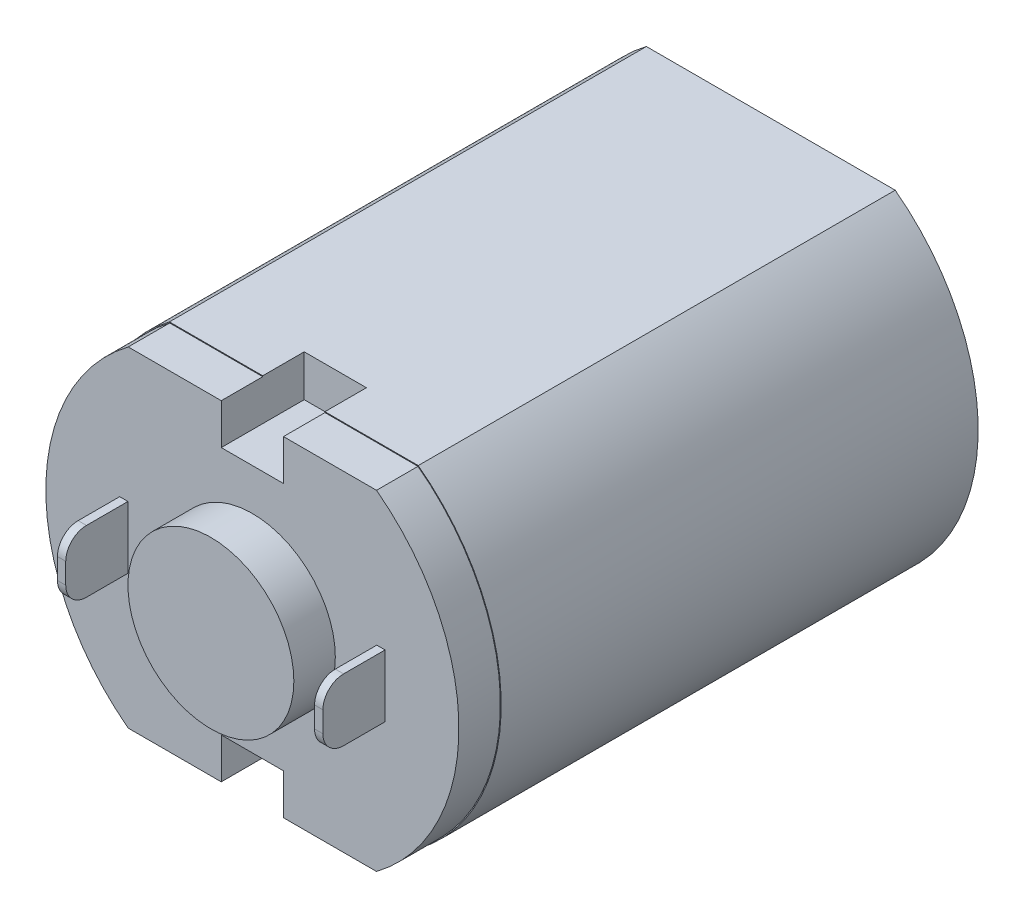
SolidWorks part; units mm, degrees
ref_plane "Front Plane" through (0, 0, 0) normal (0, 0, 1) x (1, 0, 0)
ref_plane "Top Plane" through (0, 0, 0) normal (0, 1, 0) x (1, 0, 0)
ref_plane "Right Plane" through (0, 0, 0) normal (1, 0, 0) x (0, 0, -1)
sketch "Sketch1" plane through (0, 0, 0) normal (0, 0, 1) x (1, 0, 0)
  line L1 (-3, -4) -> (3, -4)
  line L3 (-3, 4) -> (3, 4)
  line L5 (-3, -4) -> (3, 4) construction
  line L6 (-3, 4) -> (3, -4) construction
  arc A0 (-3, 4) -> (-3, -4) centre (0, 0) ccw
  arc A1 (3, -4) -> (3, 4) centre (0, 0) ccw
  dimension "D1" = 10
  dimension "D2" = 8
extrude "Boss-Extrude1" add sketch "Sketch1" along normal blind 12.5
sketch "Sketch2" plane through (0, 0, 0) normal (0, 0, 1) x (1, 0, 0)
  circle A0 centre (0, 0) radius 2
  circle A1 centre (0, 0) radius 0.5
  dimension "D1" = 4
  dimension "D2" = 1
extrude "Boss-Extrude2" add sketch "Sketch2" against normal blind 0.5
extrude "Boss-Extrude3" add sketch "Sketch2<2>" against normal blind 3 contours A1
sketch "Sketch2<2>" plane through (0, 0, 0) normal (0, 0, 1) x (1, 0, 0) same geometry as "Sketch2"
extrude "Boss-Extrude4" add sketch "Sketch2<4>" along normal blind 13.5 contours A0
sketch "Sketch2<4>" plane through (0, 0, 0) normal (0, 0, 1) x (1, 0, 0) same geometry as "Sketch2"
sketch "Sketch4" plane through (0, 0, 0) normal (0, 0, 1) x (1, 0, 0)
  line L0 (3, 4) -> (-3, 4) construction
  line L1 (-0.75, 5) -> (0.75, 5)
  line L2 (-0.75, 5) -> (-0.75, 3)
  line L3 (-0.75, 3) -> (0.75, 3)
  line L4 (0.75, 5) -> (0.75, 3)
  line L5 (-0.75, 5) -> (0.75, 3) construction
  line L6 (-0.75, 3) -> (0.75, 5) construction
  line L7 (-3.1388, 0) -> (3.1388, 0) construction
  line L8 (-0.75, -3) -> (0.75, -5) construction
  line L9 (-0.75, -5) -> (0.75, -3) construction
  line L10 (0.75, -5) -> (0.75, -3)
  line L11 (-0.75, -3) -> (0.75, -3)
  line L12 (-0.75, -5) -> (-0.75, -3)
  line L13 (-0.75, -5) -> (0.75, -5)
  point P0 (0, 4)
  point P11 (0, 0)
  point P16 (0, -4)
  dimension "D1" = 1.5
  dimension "D2" = 2
extrude "Cut-Extrude1" cut sketch "Sketch4" against normal blind 2 from surface starting at face at (2, 0, 12.5)
sketch "Sketch5" plane through (0, 0, 0) normal (0, 0, 1) x (1, 0, 0)
  line L0 (0, 1.1756) -> (0, -1.1756) construction
  line L1 (3, 0.75) -> (3.2, 0.75)
  line L2 (3, 0.75) -> (3, -0.75)
  line L3 (3, -0.75) -> (3.2, -0.75)
  line L4 (3.2, 0.75) -> (3.2, -0.75)
  line L5 (3, 0.75) -> (3.2, -0.75) construction
  line L6 (3, -0.75) -> (3.2, 0.75) construction
  line L7 (-3, -0.75) -> (-3.2, 0.75) construction
  line L8 (-3, 0.75) -> (-3.2, -0.75) construction
  line L9 (-3.2, 0.75) -> (-3.2, -0.75)
  line L10 (-3, -0.75) -> (-3.2, -0.75)
  line L11 (-3, 0.75) -> (-3, -0.75)
  line L12 (-3, 0.75) -> (-3.2, 0.75)
  point P0 (3.1, 0)
  point P10 (0, 0)
  point P13 (-3.1, 0)
  dimension "D1" = 1.5
  dimension "D2" = 0.2
  dimension "D3" = 3
extrude "Boss-Extrude5" add sketch "Sketch5" along normal blind 1.5 from surface starting at face at (2, 0, 12.5)
fillet "Fillet1" radius 0.5 4 edges at (3.1, 0.75, 14) (3.1, -0.75, 14) (-3.1, 0.75, 14) (-3.1, -0.75, 14)
sketch "Sketch6" plane through (0, 0, 0) normal (0, 0, 1) x (1, 0, 0)
  line L0 (-2.9933, -3.98) -> (2.9933, -3.98)
  line L1 (-3, -4) -> (3, -4)
  line L3 (-3, 4) -> (3, 4)
  line L5 (-2.9933, 3.98) -> (2.9933, 3.98)
  arc A0 (-3, 4) -> (-3, -4) centre (0, 0) ccw
  arc A1 (3, -4) -> (3, 4) centre (0, 0) ccw
  arc A2 (2.9933, -3.98) -> (2.9933, 3.98) centre (0, 0) ccw
  arc A3 (-2.9933, 3.98) -> (-2.9933, -3.98) centre (0, 0) ccw
  dimension "D1" = 0.02
extrude "Cut-Extrude2" cut sketch "Sketch6" against normal blind 1 from surface starting at face at (-3.1, 0, 12.5)
